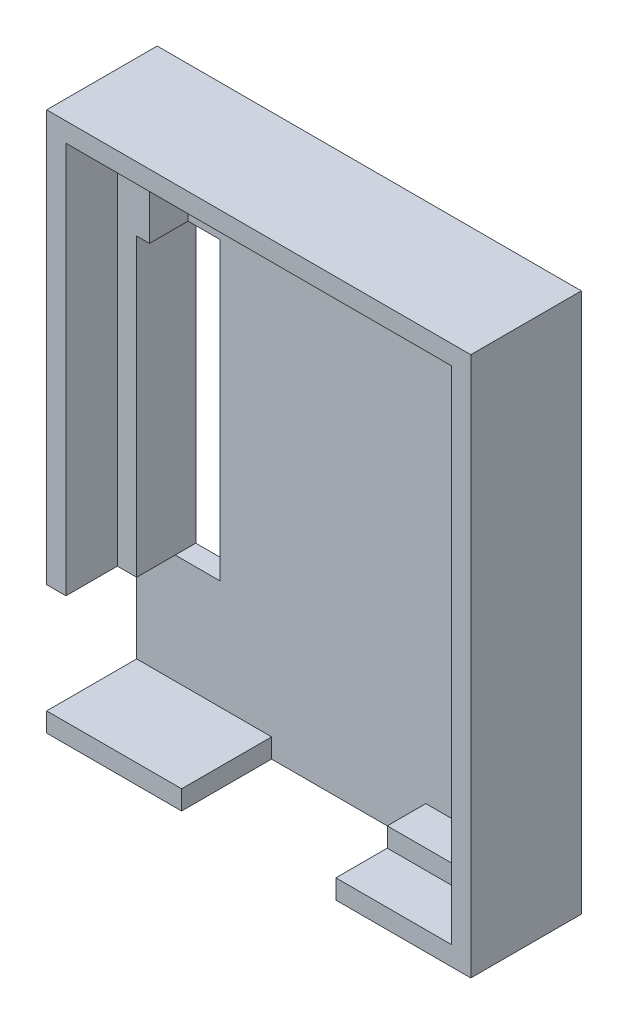
SolidWorks part; units mm, degrees
ref_plane "Plano frontal" through (0, 0, 0) normal (0, 0, 1) x (1, 0, 0)
ref_plane "Plano superior" through (0, 0, 0) normal (0, 1, 0) x (1, 0, 0)
ref_plane "Plano direito" through (0, 0, 0) normal (1, 0, 0) x (0, 0, -1)
sketch "Esboço1" plane through (0, 0, 0) normal (0, 0, 1) x (1, 0, 0)
  line L0 (0, 0) -> (10, 0)
  line L1 (0, 0) -> (-10, 0)
  line L2 (0, 0) -> (0, 24)
  line L3 (0, 24) -> (12.5, 24)
  line L4 (12.5, 24) -> (12.5, 0)
  line L5 (0, 24) -> (-12.5, 24)
  line L6 (-12.5, 24) -> (-12.5, 0)
  line L7 (-12.5, 0) -> (-12.5, -10)
  line L8 (-12.5, -10) -> (12.5, -10)
  line L9 (12.5, -10) -> (12.5, 0)
  line L10 (10, 19) -> (10, -4)
  line L11 (-10, 19) -> (-10, -4)
  line L12 (-7.5, 24) -> (-7.5, 0)
  line L13 (7.5, 24) -> (7.5, 0)
  line L14 (0, 19) -> (-7.5, 19)
  line L15 (0, 19) -> (7.5, 19)
  line L16 (0, -4) -> (13.5, -4)
  line L17 (0, -4) -> (-16.5, -4)
  line L18 (-10, 24) -> (-10, 0) construction
  line L19 (10, 24) -> (10, 0) construction
  line L20 (10, 19) -> (13.5, 19)
  line L21 (-10, 19) -> (-13.5, 19)
  line L22 (0, 19) -> (12.5, 19) construction
  line L23 (0, 25) -> (-13.5, 25)
  line L24 (0, 19) -> (-12.5, 19) construction
  line L25 (-13.5, 25) -> (-13.5, 0)
  line L26 (-13.5, 0) -> (-13.5, -11)
  line L27 (-13.5, -11) -> (13.5, -11)
  line L28 (13.5, -11) -> (13.5, 0)
  line L29 (13.5, 25) -> (13.5, 0)
  line L30 (0, 25) -> (13.5, 25)
  line L31 (0, 0) -> (-12.5, 0) construction
  line L32 (0, 0) -> (12.5, 0) construction
  line L33 (0, -4) -> (12.5, -4) construction
  line L34 (0, -4) -> (-12.5, -4) construction
  line L35 (0, 26.5) -> (-15, 26.5)
  line L36 (-15, 26.5) -> (-15, 0)
  line L37 (-15, 0) -> (-15, -12.5)
  line L38 (-16.5, -12.5) -> (15, -12.5)
  line L39 (15, -12.5) -> (15, 0)
  line L40 (15, 26.5) -> (15, 0)
  line L41 (0, 26.5) -> (15, 26.5)
  line L42 (0, -12.5) -> (0, -4)
  line L43 (6, -14) -> (6, -4)
  line L44 (-6, -14) -> (-6, -4)
  line L45 (0, 28) -> (16.5, 28)
  line L46 (16.5, 28) -> (16.5, 0)
  line L47 (16.5, -14) -> (16.5, 0)
  line L48 (-16.5, -14) -> (16.5, -14)
  line L49 (-16.5, 0) -> (-16.5, -14)
  line L50 (-16.5, 28) -> (-16.5, 0)
  line L51 (0, 28) -> (-16.5, 28)
  line L52 (-15, -12.5) -> (15, -12.5) construction
  line L53 (-6, -12.5) -> (-6, -4) construction
  line L54 (6, -12.5) -> (6, -4) construction
extrude "Ressalto-extrusão5" add sketch "Esboço1" against normal blind 1.6 contours L45 L51 L50 L49 L17 L37 L36 L35 L41 L40 L39 L38 L43 L48 L47 L46 | L43 L38 L39 L40 L41 L35 L36 L37 L17 L26 L25 L23 L30 L29 L28 L27 | L30 L23 L25 L21 L6 L5 L3 L4 L20 L29 | L21 L11 L1 L12 L5 L6 | L14 L2 L5 L12 | L2 L15 L13 L3 | L10 L20 L4 L3 L13 L0 | L15 L2 L0 L13 | L2 L14 L12 L1 | L17 L16 L10 L0 L1 L11 | L8 L44 L17 L7 | L44 L8 L42 L17 | L8 L43 L16 L42 | L43 L8 L9 L16 | L38 L43 L27 L42 | L43 L27 L28 L16 L9 L8 | L27 L43 L8 L42 | L44 L27 L42 L8 | L44 L38 L42 L27 | L38 L44 L27 L26 L17 L37 | L27 L44 L8 L7 L17 L26 | L17 L49 L38 L37 | L38 L49 L48 L44 | L44 L48 L43 L38 region at (3.75, 9.5, 0) region at (0, -2, 0) region at (-3.75, 9.5, 0) region at (9.181, 13.6379, 0) region at (-9.181, 13.6379, 0) region at (-3.75, 21.5, 0) region at (3.75, 21.5, 0) region at (-3.75, 24.2766, 0) region at (9.25, -7, 0) region at (-9.25, -7, 0) region at (3, -7, 0) region at (13, -4.1026, 0) region at (-3, -7, 0) region at (-12.6026, -7, 0) region at (13.992, 22, 0) region at (3, -10.5, 0) region at (-3, -10.5, 0) region at (-13.6238, -7.5, 0) region at (3, -11.75, 0) region at (-3, -11.75, 0) region at (-15.75, -8.25, 0) region at (-15.75, -3.4659, 0) region at (0, -13.25, 0) region at (-11.25, -13.25, 0)
extrude "Ressalto-extrusão6" add sketch "Esboço1<4>" along normal blind 7 contours L45 L51 L50 L49 L17 L37 L36 L35 L41 L40 L39 L38 L43 L48 L47 L46 | L38 L49 L48 L44 region at (-15.75, -3.4659, 0) region at (-11.25, -13.25, 0)
sketch "Esboço1<4>" plane through (0, 0, 0) normal (0, 0, 1) x (1, 0, 0) same geometry as "Esboço1"
extrude "Ressalto-extrusão7" add sketch "Esboço1<5>" along normal blind 3 contours L43 L38 L39 L40 L41 L35 L36 L37 L17 L26 L25 L23 L30 L29 L28 L27 | L30 L23 L25 L21 L6 L5 L3 L4 L20 L29 region at (-3.75, 24.2766, 0) region at (13.992, 22, 0)
sketch "Esboço1<5>" plane through (0, 0, 0) normal (0, 0, 1) x (1, 0, 0) same geometry as "Esboço1"
